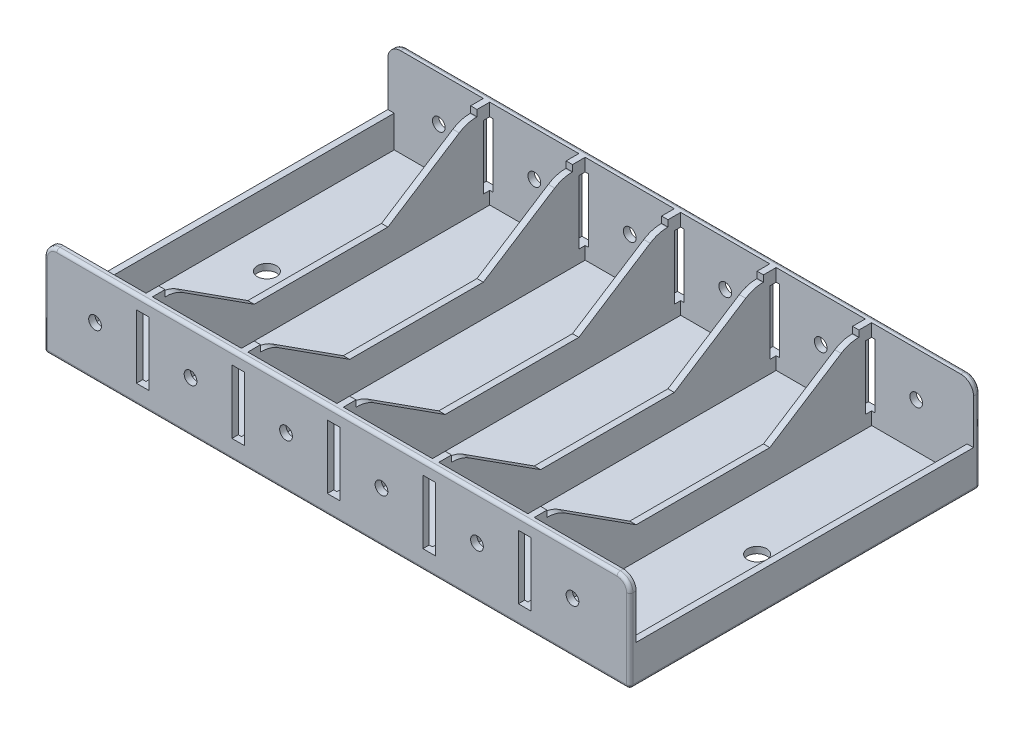
SolidWorks part; units mm, degrees
ref_plane "Front Plane" through (0, 0, 0) normal (0, 0, 1) x (1, 0, 0)
ref_plane "Top Plane" through (0, 0, 0) normal (0, 1, 0) x (1, 0, 0)
ref_plane "Right Plane" through (0, 0, 0) normal (1, 0, 0) x (0, 0, -1)
sketch "Sketch1" plane through (0, 0, 0) normal (0, 1, 0) x (1, 0, 0)
  line L1 (0, 0) -> (92, 0)
  line L2 (0, 0) -> (0, 55)
  line L3 (0, 55) -> (92, 55)
  line L4 (92, 0) -> (92, 55)
  dimension "D1" = 55
  dimension "D2" = 92
extrude "Boss-Extrude1" add sketch "Sketch1" along normal blind 15
sketch "Sketch2" plane through (0, 15, 0) normal (0, 1, 0) x (1, 0, 0)
  line L8 (1, 54) -> (1, 1)
  line L9 (1, 1) -> (91, 1)
  line L10 (91, 1) -> (91, 54)
  line L11 (91, 54) -> (1, 54)
  line L12 (1, 54) -> (1, 1)
  line L13 (1, 1) -> (91, 1)
  line L14 (91, 1) -> (91, 54)
  line L15 (91, 54) -> (1, 54)
  dimension "D1" = 1
extrude "Cut-Extrude1" cut sketch "Sketch2" against normal offset from surface (14 mm away) 1 up to face at (46, 0, -27.5)
sketch "Sketch3" plane through (0, 1, 0) normal (0, 1, 0) x (1, 0, 0)
  line L0 (91, 54) -> (1, 54) construction
  line L1 (15, 54) -> (16, 54)
  line L2 (15, 54) -> (15, 1)
  line L3 (15, 1) -> (16, 1)
  line L4 (16, 54) -> (16, 1)
  line L5 (1, 1) -> (91, 1) construction
  line L6 (1, 54) -> (1, 1) construction
  line L7 (31, 54) -> (31, 1)
  line L8 (30, 1) -> (31, 1)
  line L9 (30, 54) -> (30, 1)
  line L10 (30, 54) -> (31, 54)
  line L11 (46, 54) -> (46, 1)
  line L12 (45, 1) -> (46, 1)
  line L13 (45, 54) -> (45, 1)
  line L14 (45, 54) -> (46, 54)
  line L15 (61, 54) -> (61, 1)
  line L16 (60, 1) -> (61, 1)
  line L17 (60, 54) -> (60, 1)
  line L18 (60, 54) -> (61, 54)
  line L19 (76, 54) -> (76, 1)
  line L20 (75, 1) -> (76, 1)
  line L21 (75, 54) -> (75, 1)
  line L22 (75, 54) -> (76, 54)
  dimension "D1" = 14
  dimension "D2" = 1
  dimension "D3" = 5
extrude "Boss-Extrude2" add sketch "Sketch3" along normal up to surface (14 mm away) up to face at (46, 15, -27.5)
sketch "Sketch4" plane through (15, 0, 0) normal (-1, 0, 0) x (0, 0, 1)
  line L0 (-54, 15) -> (-52, 15)
  line L1 (-55, 15) -> (0, 15) construction
  line L2 (-52, 15) -> (-38, 6)
  line L3 (-27.5, 15) -> (-27.5, 0) construction
  line L4 (-55, 0) -> (0, 0) construction
  line L5 (-38, 6) -> (-17, 6)
  line L6 (-54, 1) -> (-1, 1) construction
  line L7 (-3, 15) -> (-17, 6)
  line L8 (-1, 15) -> (-3, 15)
  point P14 (-27.5, 6)
  line M7 (-1, 15) -> (-54, 15)
  dimension "D1" = 5
  dimension "D2" = 2
  dimension "D3" = 16
extrude "Cut-Extrude2" cut sketch "Sketch4" against normal through all and the other way through all contours L3 L2 L5 M7 | L3 L5 L7 M7 region at (15, 11.1, -36.7167) region at (15, 11.1, -18.2833)
sketch "Sketch6" plane through (0, 6, 0) normal (0, 1, 0) x (1, 0, 0)
  line L0 (0, 3) -> (0, 0) construction
  line L1 (1, 54) -> (0, 54)
  line L2 (1, 54) -> (1, 1)
  line L3 (1, 1) -> (0, 1)
  line L4 (0, 54) -> (0, 1)
  line L5 (92, 52) -> (92, 55) construction
  line L6 (91, 1) -> (92, 1)
  line L7 (91, 1) -> (91, 54)
  line L8 (91, 54) -> (92, 54)
  line L9 (92, 1) -> (92, 54)
extrude "Cut-Extrude3" cut sketch "Sketch6" along normal through all
fillet "Fillet1" radius 0.5 10 edges at (92, 7.5, -55) (46, 15, -55) (0, 7.5, -55) (0, 7.5, 0) (46, 15, 0) (92, 7.5, 0) (46, 0, 0) (92, 0, -27.5) (46, 0, -55) (0, 0, -27.5)
sketch "Sketch7" plane through (0, 1, 0) normal (0, 1, 0) x (1, 0, 0)
  line L0 (1, 27.5) -> (91, 27.5) construction
  line L1 (1, 54) -> (1, 1) construction
  line L2 (91, 1) -> (91, 54) construction
  line L3 (0, 54.5) -> (0, 0.5) construction
  line L6 (46, 55) -> (46, 0) construction
  line L7 (0.5, 55) -> (91.5, 55) construction
  line L8 (91.5, 0) -> (0.5, 0) construction
  circle A0 centre (7.5, 27.5) radius 1.5
  circle A1 centre (84.5, 27.5) radius 1.5
  dimension "D1" = 3
  dimension "D2" = 7.5
extrude "Cut-Extrude4" cut sketch "Sketch7" against normal blind 1
sketch "Sketch8" plane through (0, 0, 0) normal (0, 0, 1) x (1, 0, 0)
  line L0 (15, 8) -> (16, 8) construction
  line L1 (14.5, 13) -> (16.5, 13)
  line L2 (14.5, 13) -> (14.5, 3)
  line L3 (14.5, 3) -> (16.5, 3)
  line L4 (16.5, 13) -> (16.5, 3)
  line L5 (15, 15) -> (15, 1) construction
  line L6 (16, 15) -> (16, 1) construction
  line L7 (14.5, 8) -> (16.5, 8) construction
  line L8 (15.5, 13) -> (15.5, 3) construction
  point P13 (15.5, 8)
  dimension "D1" = 2
  dimension "D2" = 10
extrude "Cut-Extrude6" cut sketch "Sketch8" against normal blind 2
pattern_linear "LPattern2" count 5 spacing 15 along (1, 0, 0) of "Cut-Extrude6"
ref_plane "Plane2" through (0, 0, -27.5) normal (0, 0, 1) x (1, 0, 0)
mirror "Mirror2" about plane through (0, 0, -27.5) normal (0, 0, 1) of "LPattern2"
sketch "Sketch9" plane through (0, 0, 0) normal (0, -1, 0) x (1, 0, 0)
  line L0 (91.5, -0.5) -> (0.5, -0.5) construction
  line L1 (90.5, -1.5) -> (20.5, -1.5)
  line L2 (90.5, -1.5) -> (90.5, -3.5)
  line L3 (90.5, -3.5) -> (20.5, -3.5)
  line L4 (20.5, -1.5) -> (20.5, -3.5)
  line L5 (91.5, -54.5) -> (91.5, -0.5) construction
  dimension "D1" = 1
  dimension "D2" = 1
  dimension "D3" = 2
  dimension "D4" = 70
extrude "Cut-Extrude7" cut sketch "Sketch9" against normal blind 0.5
sketch "Sketch10" plane through (0, 0, 0) normal (0, 0, 1) x (1, 0, 0)
  line L0 (15.5, 13) -> (30.5, 13) construction
  line L1 (16.5, 13) -> (14.5, 13) construction
  line L2 (31.5, 13) -> (29.5, 13) construction
  line L3 (15.5, 3) -> (30.5, 3) construction
  line L4 (15, 3) -> (16, 3) construction
  line L5 (29.5, 3) -> (31.5, 3) construction
  line L6 (23, 13) -> (23, 3) construction
  circle A0 centre (23, 8) radius 1
  circle A1 centre (38, 8) radius 1
  circle A2 centre (53, 8) radius 1
  circle A3 centre (68, 8) radius 1
  circle A4 centre (83, 8) radius 1
  circle A5 centre (8, 8) radius 1
  dimension "D1" = 2
  dimension "D2" = 5
  dimension "D3" = 2
extrude "Cut-Extrude8" cut sketch "Sketch10" against normal through all
fillet "Fillet2" radius 2 8 edges at (0.1464, 14.8536, -0.1464) (0.1464, 14.8536, -54.8536) (91.8536, 14.8536, -0.1464) (91.8536, 14.8536, -54.8536) (92, 15, -54.25) (92, 15, -0.75) (0, 15, -54.25) (0, 15, -0.75)
sketch "Sketch11" plane through (76, 0, 0) normal (1, 0, 0) x (0, 0, -1)
  line L0 (3, 15) -> (1, 15) construction
  line L1 (3, 15) -> (52, 15)
  line L2 (3, 15) -> (3, 14)
  line L3 (3, 14) -> (52, 14)
  line L4 (52, 15) -> (52, 14)
  line L5 (1, 13) -> (1, 15) construction
  line L6 (52, 15) -> (38, 6) construction
  line L7 (54, 15) -> (52, 15) construction
  point P6 (1, 14)
  dimension "D1" = 1
  dimension "D2" = 2
extrude "Cut-Extrude9" cut sketch "Sketch11" against normal through all
fillet "Fillet3" radius 5 10 edges at (75.5, 14, -50.4444) (60.5, 14, -50.4444) (45.5, 14, -50.4444) (30.5, 14, -50.4444) (15.5, 14, -50.4444) (15.5, 14, -4.5556) (30.5, 14, -4.5556) (45.5, 14, -4.5556) (75.5, 14, -4.5556) (60.5, 14, -4.5556)
